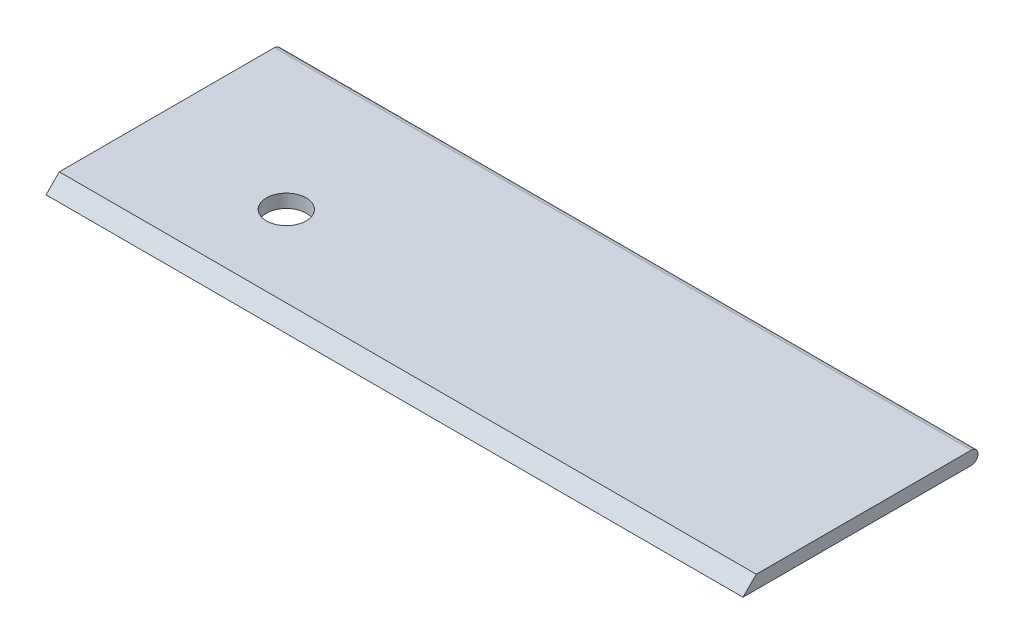
SolidWorks part; units mm, degrees
ref_plane "Front Plane" through (0, 0, 0) normal (0, 0, 1) x (1, 0, 0)
ref_plane "Top Plane" through (0, 0, 0) normal (0, 1, 0) x (1, 0, 0)
ref_plane "Right Plane" through (0, 0, 0) normal (1, 0, 0) x (0, 0, -1)
sketch "Sketch1" plane through (0, 0, 0) normal (0, 1, 0) x (1, 0, 0)
  line L1 (0, 0) -> (133.35, 0)
  line L2 (0, 0) -> (0, -44.958)
  line L3 (0, -44.958) -> (133.35, -44.958)
  line L4 (133.35, 0) -> (133.35, -44.958)
  dimension "D1" = 133.35
  dimension "D2" = 44.958
extrude "Boss-Extrude1" add sketch "Sketch1" along normal blind 2.54
sketch "Sketch2" plane through (133.35, 0, 0) normal (1, 0, 0) x (0, 0, -1)
  line L2 (-44.958, 0) -> (-44.958, 2.54)
  line L3 (-44.958, 2.54) -> (-42.418, 2.54)
  line L5 (-44.958, 2.54) -> (0, 2.54) construction
  line L6 (-42.418, 2.54) -> (-44.958, 0)
  line L7 (-44.958, 2.54) -> (-44.958, 0) construction
  dimension "D1" = 45
extrude "Cut-Extrude1" cut sketch "Sketch2" against normal through all
sketch "Sketch6" plane through (0, 2.54, 0) normal (0, 1, 0) x (1, 0, 0)
  line L0 (0, 0) -> (0, -42.418) construction
  line L2 (133.35, 0) -> (0, 0) construction
  circle A0 centre (27.94, -26.924) radius 3.81
  dimension "D1" = 27.94
  dimension "D3" = 7.62
  dimension "D2" = 26.924
extrude "Cut-Extrude3" cut sketch "Sketch6" against normal through all
sketch "Sketch7" plane through (0, 0, 0) normal (0, -1, 0) x (1, 0, 0)
  line L0 (133.35, 44.958) -> (133.35, 0) construction
  line L1 (99.568, 27.94) -> (102.108, 27.94)
  line L2 (99.568, 27.94) -> (99.568, 22.86)
  line L3 (99.568, 22.86) -> (102.108, 22.86)
  line L4 (102.108, 27.94) -> (102.108, 22.86)
  line L5 (133.35, 0) -> (0, 0) construction
  dimension "D1" = 31.242
  dimension "D2" = 2.54
  dimension "D3" = 5.08
  dimension "D4" = 22.86
extrude "Boss-Extrude2" add sketch "Sketch7" along normal blind 4.572
sketch "Sketch9" plane through (99.568, 0, 0) normal (-1, 0, 0) x (0, 0, 1)
  line L0 (25.4, 0) -> (25.4, -4.572) construction
  line L1 (27.94, 0) -> (22.86, 0) construction
  line L2 (27.94, -4.572) -> (22.86, -4.572) construction
  circle A0 centre (25.4, -2.286) radius 0.762
  dimension "D1" = 1.524
extrude "Cut-Extrude4" cut sketch "Sketch9" against normal through all
fillet "Fillet2" radius 2.54 1 edges at (100.838, -4.572, 27.94)
fillet "Fillet3" radius 2.54 1 edges at (100.838, -4.572, 22.86)
fillet "Fillet4" radius 1.27 2 edges at (66.675, 0, 0) (66.675, 2.54, 0)
sketch "Sketch16" plane through (0, 0, 0) normal (0, -1, 0) x (1, 0, 0)
  line L0 (0, 5.9436) -> (20.955, 5.9436) construction
  line L1 (0, 1.27) -> (0, 44.958) construction
  line L2 (20.955, 5.9436) -> (30.9626, 5.9436) construction
  line L3 (133.35, 5.9436) -> (112.395, 5.9436) construction
  line L4 (133.35, 44.958) -> (133.35, 1.27) construction
  line L5 (112.395, 5.9436) -> (102.3874, 5.9436) construction
  line L7 (133.35, 0) -> (0, 0) construction
  circle A0 centre (20.955, 5.9436) radius 1.4986
  circle A1 centre (30.9626, 5.9436) radius 1.4986
  circle A2 centre (102.3874, 5.9436) radius 1.4986
  circle A3 centre (112.395, 5.9436) radius 1.4986
  dimension "D4" = 2.9972
  dimension "D5" = 2.9972
  dimension "D6" = 2.9972
  dimension "D7" = 2.9972
  dimension "D1" = 10.0076
  dimension "D2" = 20.955
  dimension "D3" = 5.9436
extrude "Cut-Extrude8" cut sketch "Sketch16" against normal blind 2.032
sketch "Sketch17" plane through (0, 0, 0) normal (0, 1, 0) x (1, 0, 0)
  line L1 (40.64, -14.224) -> (15.24, -14.224)
  line L2 (40.64, -14.224) -> (40.64, -39.624)
  line L3 (40.64, -39.624) -> (15.24, -39.624)
  line L4 (15.24, -14.224) -> (15.24, -39.624)
  line L5 (40.64, -14.224) -> (15.24, -39.624) construction
  line L6 (40.64, -39.624) -> (15.24, -14.224) construction
  circle A0 centre (38.1, -16.764) radius 1.524
  circle A1 centre (17.78, -16.764) radius 1.524
  point P0 (27.94, -26.924)
  dimension "D3" = 2.54
  dimension "D4" = 3.048
  dimension "D6" = 3.048
  dimension "D1" = 25.4
  dimension "D2" = 25.4
  dimension "D5" = 2.54
  dimension "D7" = 2.54
  dimension "D8" = 2.54
extrude "Cut-Extrude9" cut sketch "Sketch17" along normal blind 2.032 contours A0 | A1
